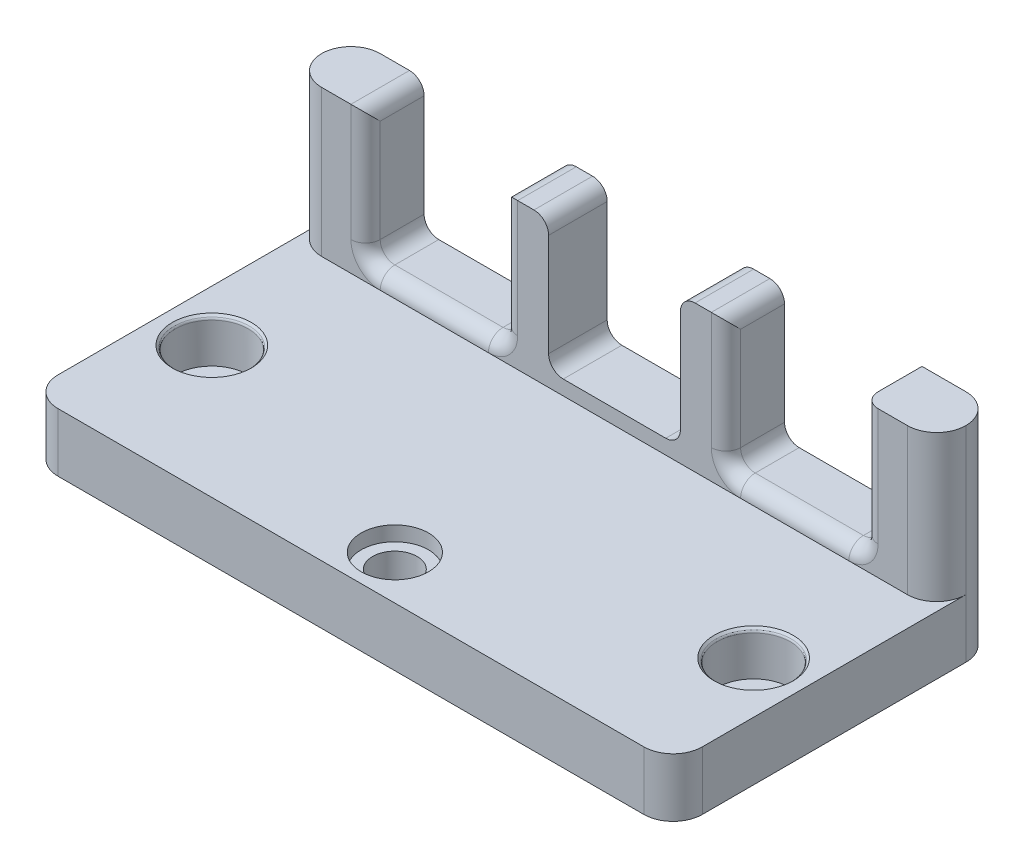
SolidWorks part; units mm, degrees
ref_plane "Front Plane" through (0, 0, 0) normal (0, 0, 1) x (1, 0, 0)
ref_plane "Top Plane" through (0, 0, 0) normal (0, 1, 0) x (1, 0, 0)
ref_plane "Right Plane" through (0, 0, 0) normal (1, 0, 0) x (0, 0, -1)
sketch "Sketch1" plane through (0, 0, 0) normal (0, 1, 0) x (1, 0, 0)
  line L1 (0, 0) -> (220, 0)
  line L2 (0, 0) -> (0, 110)
  line L3 (0, 110) -> (220, 110)
  line L4 (220, 0) -> (220, 110)
  dimension "D1" = 220
  dimension "D2" = 110
extrude "Boss-Extrude1" add sketch "Sketch1" along normal blind 20
sketch "Sketch2" plane through (0, 20, 0) normal (0, 1, 0) x (1, 0, 0)
  line L0 (0, 45) -> (220, 45) construction
  line L1 (0, 110) -> (0, 0) construction
  line L2 (220, 0) -> (220, 110) construction
  line L3 (0, 0) -> (220, 0) construction
  line L4 (110, 45) -> (110, 110) construction
  line L5 (220, 110) -> (0, 110) construction
  circle A0 centre (17.5, 45) radius 12.49
  circle A1 centre (202.5, 45) radius 12.49
  circle A2 centre (110, 15) radius 7.6
  point P10 (110, 45)
  dimension "D2" = 24.98
  dimension "D4" = 15
  dimension "D5" = 15.2
  dimension "D1" = 45
  dimension "D3" = 92.5
extrude "Cut-Extrude1" cut sketch "Sketch2" against normal blind 15
sketch "Sketch3" plane through (0, 20, 0) normal (0, 1, 0) x (1, 0, 0)
  line L0 (220, 0) -> (220, 110) construction
  line L1 (0, 110) -> (220, 110)
  line L2 (0, 110) -> (0, 90)
  line L3 (0, 90) -> (220, 90)
  line L4 (220, 110) -> (220, 90)
  dimension "D1" = 20
extrude "Boss-Extrude2" add sketch "Sketch3" along normal blind 50
chamfer "Chamfer1" distance 1 angle 45 2 edges at (202.5, 20, -57.49) (17.5, 20, -32.51)
fillet "Fillet1" radius 1 2 edges at (202.5, 19, -57.49) (17.5, 19, -57.49)
fillet "Fillet2" radius 10 6 edges at (220, 45, -90) (0, 45, -90) (0, 35, -110) (0, 10, 0) (220, 35, -110) (220, 10, 0)
sketch "Sketch4" plane through (0, 20, 0) normal (0, 1, 0) x (1, 0, 0)
  circle A0 centre (110, 15) radius 11.5
  dimension "D1" = 23
extrude "Cut-Extrude2" cut sketch "Sketch4" against normal blind 5
sketch "Sketch5" plane through (0, 0, -110) normal (0, 0, -1) x (-1, 0, 0)
  line L0 (-195, 70) -> (-25, 70)
  line L1 (-210, 70) -> (-10, 70) construction
  line L2 (-110, 70) -> (-110, 27.057) construction
  line L7 (-195, 70) -> (-195, 0) construction
  line L8 (-210, 0) -> (-10, 0) construction
  line L9 (-25, 70) -> (-25, 0) construction
  line L10 (-195, 85) -> (-148.0592, 85)
  line L11 (-25, 25) -> (-71.9408, 25)
  line L12 (-25, 25) -> (-25, 85)
  line L13 (-25, 85) -> (-71.9408, 85)
  line L14 (-71.9408, 25) -> (-71.9408, 85)
  line L15 (-148.0592, 25) -> (-148.0592, 85)
  line L16 (-195, 25) -> (-148.0592, 25)
  line L17 (-195, 25) -> (-195, 85)
  line L19 (-132.5, 115) -> (-87.5, 115)
  line L20 (-132.5, 115) -> (-132.5, 25)
  line L21 (-132.5, 25) -> (-87.5, 25)
  line L22 (-87.5, 115) -> (-87.5, 25)
  line L23 (-132.5, 115) -> (-87.5, 25) construction
  line L24 (-132.5, 25) -> (-87.5, 115) construction
  point P5 (-110, 70)
  dimension "D1" = 170
  dimension "D2" = 46.9408
  dimension "D3" = 60
  dimension "D4" = 15
  dimension "D5" = 45
  dimension "D6" = 90
extrude "Cut-Extrude3" cut sketch "Sketch5" against normal through all contours L10 L15 L16 L17 | L20 L19 L22 L21 | L12 L11 L14 L13
fillet "Fillet4" radius 5 17 edges at (195, 47.5, -90) (148.0592, 47.5, -90) (25, 47.5, -90) (71.9408, 47.5, -90) (171.5296, 25, -90) (48.4704, 25, -90) (25, 70, -100) (25, 25, -100) (71.9408, 25, -100) (71.9408, 70, -100) (87.5, 70, -100) (87.5, 25, -100) (132.5, 25, -100) (132.5, 70, -100) (148.0592, 70, -100) (148.0592, 25, -100) (195, 25, -100)
sketch "Sketch6" plane through (0, 0, -110) normal (0, 0, -1) x (-1, 0, 0)
  line L0 (-110, 25) -> (-110, 0) construction
  line L1 (-127.5, 25) -> (-92.5, 25) construction
  line L2 (-210, 0) -> (-10, 0) construction
  circle A0 centre (-110, 12.5) radius 3.2
  dimension "D1" = 6.4
extrude "Cut-Extrude4" cut sketch "Sketch6" against normal blind 10
